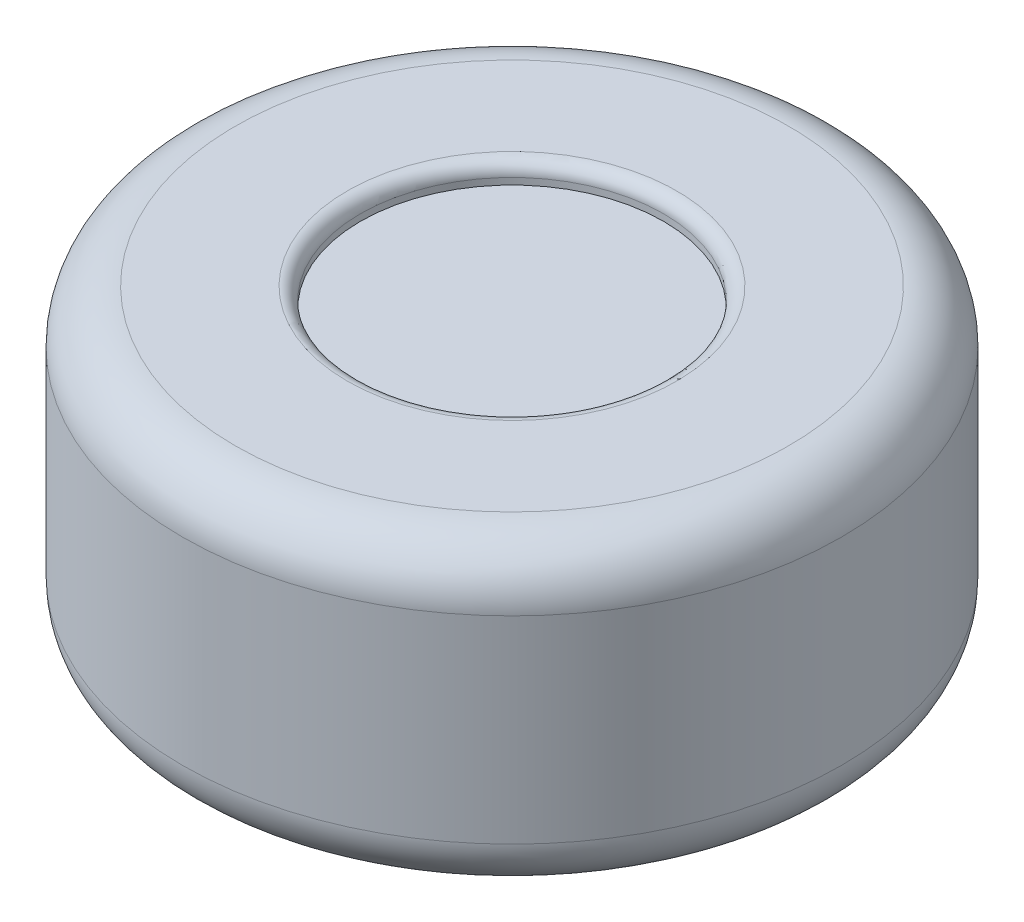
SolidWorks part; units mm, degrees
ref_plane "Alzado" through (0, 0, 0) normal (0, 0, 1) x (1, 0, 0)
ref_plane "Planta" through (0, 0, 0) normal (0, 1, 0) x (1, 0, 0)
ref_plane "Vista lateral" through (0, 0, 0) normal (1, 0, 0) x (0, 0, -1)
sketch "Croquis1" plane through (0, 0, 0) normal (0, 1, 0) x (1, 0, 0)
  circle A0 centre (0, 0) radius 120
  dimension "D1" = 240
extrude "Saliente-Extruir1" add sketch "Croquis1" along normal blind 100 and the other way blind 100
sketch "Croquis3" plane through (0, 0, 0) normal (0, 1, 0) x (1, 0, 0)
  circle A0 centre (0, 0) radius 250
  circle A1 centre (0, 0) radius 115
  dimension "D1" = 500
  dimension "D2" = 0
  dimension "D3" = 230
extrude "Saliente-Extruir4" add sketch "Croquis3" along normal blind 115 and the other way blind 115
fillet "Redondeo1" radius 40 2 edges at (0, 115, 250) (0, -115, 250)
fillet "Redondeo2" radius 10 1 edges at (0, -115, 115)
fillet "Redondeo3" radius 10 1 edges at (0, 115, 115)
